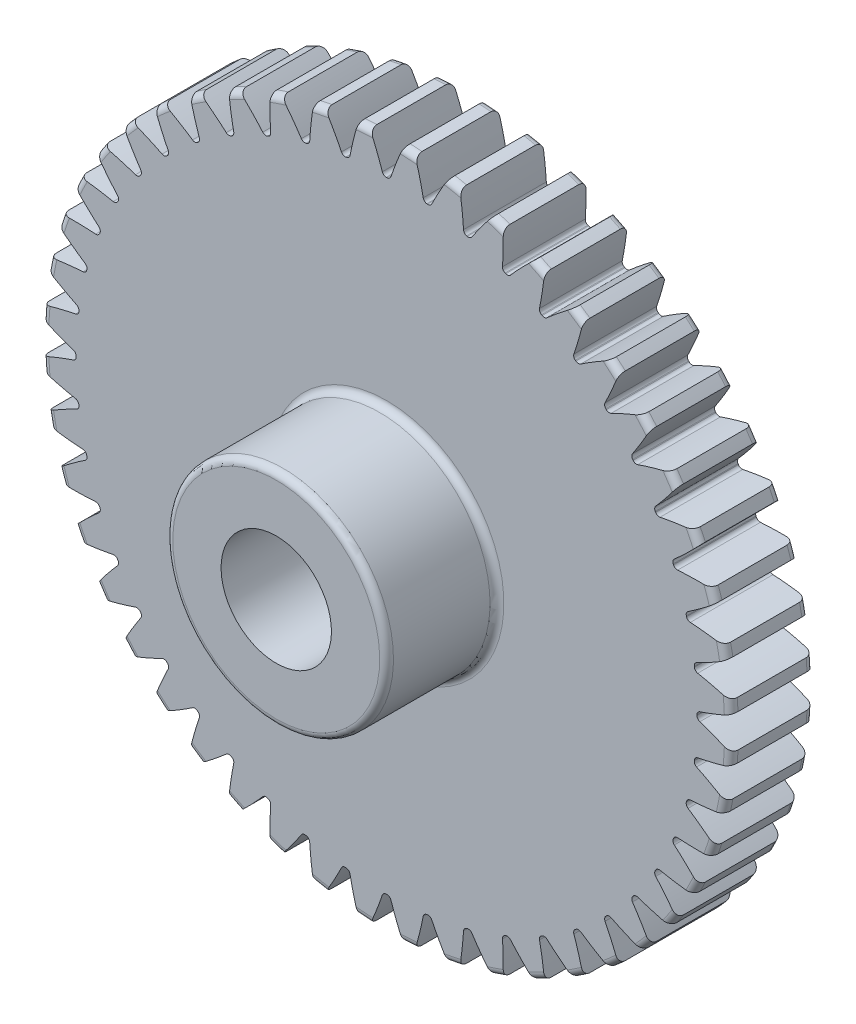
SolidWorks part; units mm, degrees
material "Delrin 2700 NC010, Low Viscosity Acetal Copolymer (SS)"
ref_plane "Front Plane" through (0, 0, 0) normal (0, 0, 1) x (1, 0, 0)
ref_plane "Top Plane" through (0, 0, 0) normal (0, 1, 0) x (1, 0, 0)
ref_plane "Right Plane" through (0, 0, 0) normal (1, 0, 0) x (0, 0, -1)
sketch "Sketch1" plane through (0, 0, 0) normal (0, 0, 1) x (1, 0, 0)
  line L0 (-609.6, 0) -> (609.6, 0) construction
  circle A0 centre (0, 0) radius 25 construction
  circle A1 centre (0, 0) radius 24 construction
  circle A2 centre (0, 0) radius 22.5 construction
  circle A3 centre (0, 0) radius 8 construction
  circle A4 centre (0, 0) radius 4 construction
  dimension "D2" = 1
  dimension "D3" = 2.5
  dimension "D1" = 2.5
sketch "Sketch2" plane through (0, 0, 0) normal (1, 0, 0) x (0, 0, -1)
  line L0 (0, 0) -> (-6, 0) construction
  line L1 (-6, 0) -> (-14, 0) construction
  dimension "Overall Width" = 14
  dimension "Face Width" = 6
sketch "Sketch4" plane through (0, 0, 0) normal (1, 0, 0) x (0, 0, -1)
  line L0 (-14, 4) -> (-14, 8)
  line L1 (-14, 8) -> (-6, 8)
  line L2 (-6, 8) -> (-6, 25)
  line L3 (-6, 25) -> (0, 25)
  line L4 (0, 25) -> (0, 4)
  line L5 (-6, 8) -> (-6, 0) construction
  line L6 (0, 25) -> (0, -25) construction
  line L7 (-6, 8) -> (0, 8) construction
  line L12 (-14, 4) -> (0, 4)
revolve "Revolve1" add sketch "Sketch4" angle 360 about L1
fillet "Fillet2" radius 0.5 4 edges at (0, 8, 14) (0, 8, 6) (0, 25, 6) (0, 25, 0)
sketch "Sketch7" plane through (0, 0, 6) normal (0, 0, 1) x (1, 0, 0)
  line L0 (0, 0) -> (0, 25) construction
  line L1 (0.7853, 23.9872) -> (1.1807, 24.9721) construction
  line L3 (1.6351, 24.9465) -> (1.5697, 23.9486) construction
  line L4 (1.5697, 23.9486) -> (1.4716, 22.4518) construction
  line L5 (0, 0) -> (1.4716, 22.4518) construction
  line L6 (0.7853, 23.9872) -> (0, 0) construction
  line L7 (0.7853, 23.9872) -> (0.818, 24.9866) construction
  line L8 (0.7853, 23.9872) -> (0, 0) construction
  circle A0 centre (0, 0) radius 25 construction
  arc A1 (-0.0275, 22.5) -> (0.0275, 22.5) centre (0, 0) cw
  circle A2 centre (0, 0) radius 22.5 construction
  arc A3 (-0.7853, 23.9872) -> (0.7853, 23.9872) centre (0, 0) cw construction
  circle A4 centre (0, 0) radius 24 construction
  arc A5 (2.0637, 24.9147) -> (1.2059, 24.9709) centre (0, 0) ccw construction
  arc A6 (0.7853, 23.9872) -> (2.3524, 23.8844) centre (0, 0) cw construction
  arc A7 (-1.2059, 24.9709) -> (1.2059, 24.9709) centre (0, 0) cw
  arc A8 (0.3122, 22.7043) -> (1.2059, 24.9709) centre (23.0572, 15.0452) cw
  arc A9 (-0.3122, 22.7043) -> (-1.2059, 24.9709) centre (-23.0572, 15.0452) ccw
  arc A10 (-0.0275, 22.5) -> (-0.3122, 22.7043) centre (-0.0278, 22.8) cw
  arc A11 (0.0275, 22.5) -> (0.3122, 22.7043) centre (0.0278, 22.8) ccw
  point P26 (-0.244, 22.4987)
  point P29 (0.244, 22.4987)
  dimension "D4" = 0.3
  dimension "D5" = 24
  dimension "D3" = 20
  dimension "D1" = 3.1416
  dimension "D2" = 1.5708
extrude "Cut-Extrude2" cut sketch "Sketch7" against normal through all
pattern_circular "CirPattern1" count 48 over 360 about axis through (0, 0, 14) along (0, 0, -1) of "Cut-Extrude2"
equation "\"D1@Sketch1\"=2.5*(\"Pitch Dia.@Sketch1\"/\"Number of Teeth@Sketch1\")"
equation "\"D1@CirPattern1\"=\"Number of Teeth@Sketch1\""
equation "\"D1@Fillet2\"=\"OD@Sketch1\"*.01"
equation "\"D1@Sketch7\"=3.14159*(\"Pitch Dia.@Sketch1\"/\"Number of Teeth@Sketch1\")"
equation "\"D2@Sketch7\"=\"D1@Sketch7\"/2"
equation "\"D4@Sketch7\"=\"D1@Sketch7\"*.0955"
equation "\"D5@Sketch7\"=\"Pitch Dia.@Sketch1\"/2"
